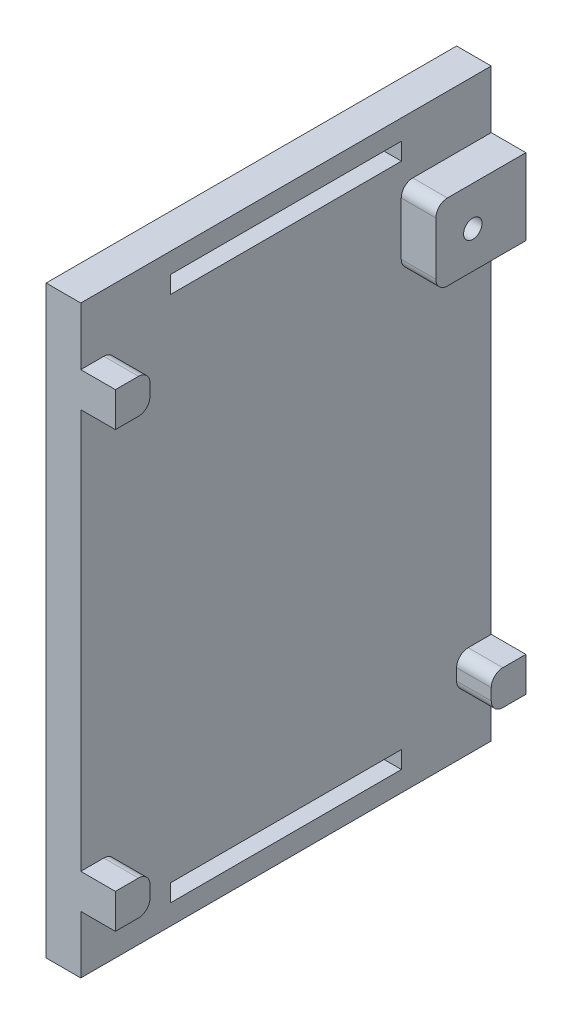
SolidWorks part; units mm, degrees
ref_plane "Front Plane" through (0, 0, 0) normal (1, 0, 0) x (0, 1, 0)
ref_plane "Top Plane" through (0, 0, 0) normal (0, 0, 1) x (0, 1, 0)
ref_plane "Right Plane" through (0, 0, 0) normal (0, 1, 0) x (-1, 0, 0)
sketch "Sketch1" plane through (0, 0, 0) normal (1, 0, 0) x (0, 1, 0)
  line L10 (-20.32, 17.78) -> (20.32, 17.78) construction
  line L11 (-20.32, 17.78) -> (-20.32, -17.78) construction
  line L18 (-20.32, -17.78) -> (20.32, -17.78) construction
  line L19 (20.32, 17.78) -> (20.32, -17.78) construction
  line L20 (-20.32, 17.78) -> (20.32, -17.78) construction
  line L21 (-20.32, -17.78) -> (20.32, 17.78) construction
  line L22 (-25.32, 17.78) -> (25.32, 17.78)
  line L23 (-25.32, 17.78) -> (-25.32, -17.78)
  line L24 (-25.32, -17.78) -> (25.32, -17.78)
  line L25 (25.32, 17.78) -> (25.32, -17.78)
  line L26 (-25.32, 17.78) -> (25.32, -17.78) construction
  line L27 (-25.32, -17.78) -> (25.32, 17.78) construction
  point P0 (0, 0)
  point P5 (0, 0)
  dimension "D1" = 40.64
  dimension "D2" = 35.56
  dimension "D3" = 5
extrude "Boss-Extrude1" add sketch "Sketch1" along normal blind 3 contours L25 L22 L23 L24 region at (0, 0, 0)
sketch "Sketch2" plane through (3, 0, 0) normal (1, 0, 0) x (0, 1, 0)
  line L0 (-25.32, -17.78) -> (25.32, -17.78) construction
  line L1 (-25.32, 17.78) -> (-20.32, 17.78)
  line L2 (-25.32, 17.78) -> (-25.32, -17.78)
  line L3 (-25.32, -17.78) -> (-20.32, -17.78)
  line L4 (-20.32, 17.78) -> (-20.32, -17.78)
  line L5 (-22.82, 17.78) -> (-22.82, -49982.22) construction
  line L6 (25.32, 17.78) -> (20.32, 17.78)
  line L7 (25.32, 17.78) -> (25.32, -17.78)
  line L8 (25.32, -17.78) -> (20.32, -17.78)
  line L9 (20.32, 17.78) -> (20.32, -17.78)
  line L10 (0, 17.78) -> (0, -49982.22) construction
  line L11 (-25.32, 17.78) -> (25.32, 17.78) construction
  line L12 (-22.82, 0) -> (-20.32, 0) construction
  line L13 (-23.57, -10) -> (-22.07, -10)
  line L14 (-23.57, -10) -> (-23.57, 10)
  line L15 (-23.57, 10) -> (-22.07, 10)
  line L16 (-22.07, -10) -> (-22.07, 10)
  line L17 (-23.57, -10) -> (-22.07, 10) construction
  line L18 (-23.57, 10) -> (-22.07, -10) construction
  line L19 (23.57, 10) -> (22.07, -10) construction
  line L20 (23.57, -10) -> (22.07, 10) construction
  line L21 (22.07, -10) -> (22.07, 10)
  line L22 (23.57, 10) -> (22.07, 10)
  line L23 (23.57, -10) -> (23.57, 10)
  line L24 (23.57, -10) -> (22.07, -10)
  point P14 (-22.82, 17.78)
  point P19 (0, 17.78)
  point P20 (-22.82, 0)
  point P31 (22.82, 0)
  dimension "D1" = 5
  dimension "D2" = 1.5
  dimension "D3" = 20
extrude "Cut-Extrude1" cut sketch "Sketch2" against normal through all both and the other way through all contours L23 L22 L21 L24 | L14 L15 L16 L13
sketch "Sketch3" plane through (3, 0, 0) normal (1, 0, 0) x (0, 1, 0)
  line L0 (-25.32, 17.78) -> (25.32, 17.78) construction
  line L1 (-20.32, -17.78) -> (20.32, -17.78) construction
  line L2 (-20.32, -17.78) -> (-20.32, 17.78) construction
  line L3 (-20.32, 17.78) -> (20.32, 17.78) construction
  line L4 (20.32, -17.78) -> (20.32, 17.78) construction
  line L5 (-20.32, -17.78) -> (20.32, 17.78) construction
  line L6 (-20.32, 17.78) -> (20.32, -17.78) construction
  line L7 (0, 0) -> (0, 50000) construction
  line L8 (-20.32, 17.78) -> (-17.32, 17.78)
  line L9 (-20.32, 17.78) -> (-20.32, 14.78)
  line L10 (-20.32, 14.78) -> (-17.32, 14.78)
  line L11 (-17.32, 17.78) -> (-17.32, 14.78)
  line L12 (0, 0) -> (50000, 0) construction
  line L13 (-20.32, -14.78) -> (-17.32, -14.78)
  line L14 (-20.32, -17.78) -> (-17.32, -17.78)
  line L15 (-20.32, -17.78) -> (-20.32, -14.78)
  line L16 (-17.32, -17.78) -> (-17.32, -14.78)
  line L17 (20.32, 14.78) -> (17.32, 14.78)
  line L18 (17.32, 17.78) -> (17.32, 14.78)
  line L19 (20.32, 17.78) -> (17.32, 17.78)
  line L20 (20.32, 17.78) -> (20.32, 14.78)
  line L22 (20.32, -17.78) -> (13.716, -17.78)
  line L23 (20.32, -17.78) -> (20.32, -9.983)
  line L24 (20.32, -9.983) -> (13.716, -9.983)
  line L25 (13.716, -17.78) -> (13.716, -9.983)
  circle A0 centre (16.916, -13.183) radius 0.8
  point P0 (0, 0)
  dimension "D6" = 1.6
  dimension "D8" = 3.2
  dimension "D1" = 40.64
  dimension "D2" = 3
  dimension "D3" = 3
  dimension "D4" = 3.404
  dimension "D5" = 4.597
  dimension "D7" = 3.2
extrude "Boss-Extrude2" add sketch "Sketch3" along normal blind 3
sketch "Sketch4" plane through (6, 0, 0) normal (1, 0, 0) x (0, 1, 0)
  circle A0 centre (16.916, -13.183) radius 0.8
  dimension "D1" = 1.6
extrude "Cut-Extrude2" cut sketch "Sketch4" against normal through all both and the other way through all
fillet "Fillet1" radius 1 8 edges at (4.5, -17.32, -14.78) (4.5, -20.32, -14.78) (4.5, 13.716, -9.983) (4.5, 20.32, -9.983) (4.5, 20.32, 14.78) (4.5, 17.32, 14.78) (4.5, -20.32, 14.78) (4.5, -17.32, 14.78)
equation "\"PCB_Width\"= 1.05in"
equation "\"PCB_Length\"= 1.35in"
equation "\"PCB_Thickness\"= 1.50404mm"
equation "\"USB_Height\"= 3.36mm"
equation "\"ZIF_Height\"= 2mm"
equation "\"Case_Thickness\"= 5mm"
